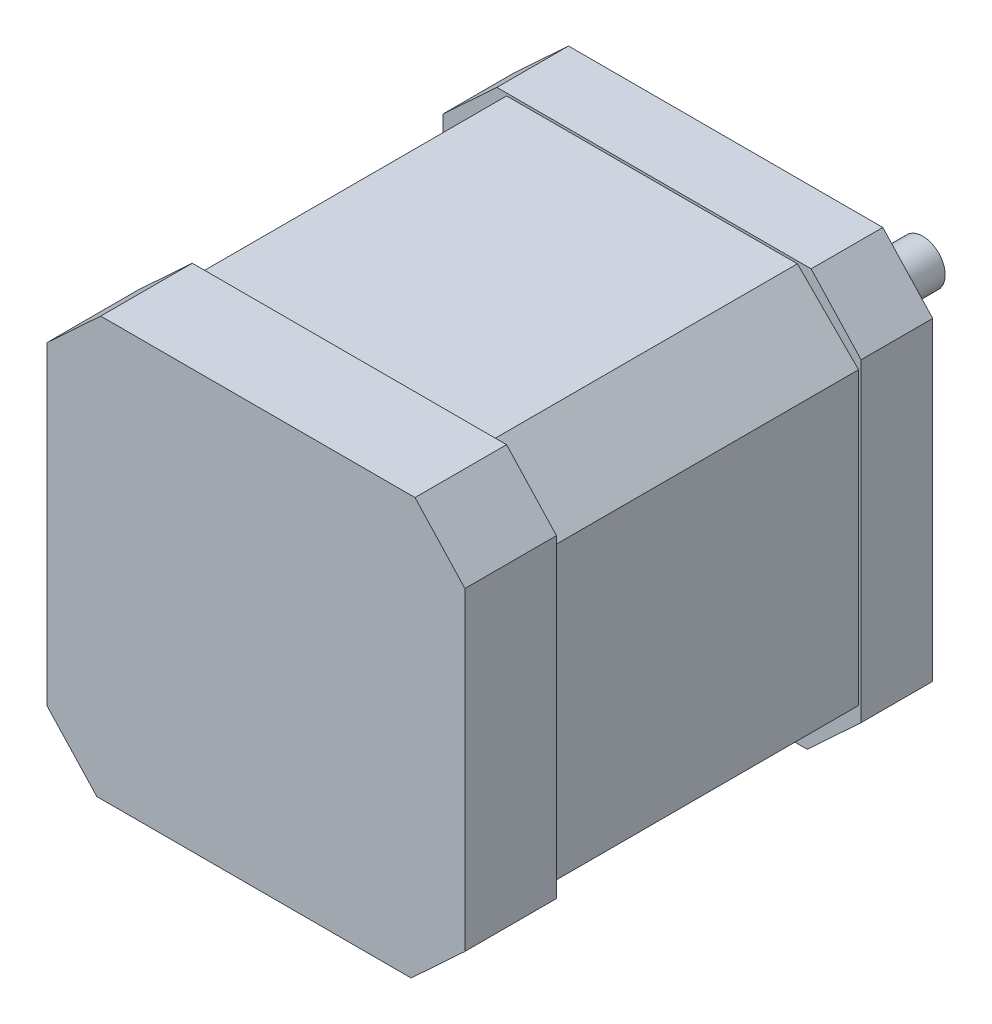
SolidWorks part; units mm, degrees
material "Ferro dúctil"
ref_plane "Plano frontal" through (0, 0, 0) normal (0, 0, 1) x (1, 0, 0)
ref_plane "Plano superior" through (0, 0, 0) normal (0, 1, 0) x (1, 0, 0)
ref_plane "Plano direito" through (0, 0, 0) normal (1, 0, 0) x (0, 0, -1)
sketch "Esboço1" plane through (0, 0, 0) normal (0, 0, 1) x (1, 0, 0)
  line L0 (-1.3818, -36.7436) -> (-36.7436, 1.3818)
  line L1 (-21, 21) -> (21, 21)
  line L2 (-21, 21) -> (-21, -21)
  line L3 (-21, -21) -> (21, -21)
  line L4 (21, 21) -> (21, -21)
  line L5 (-21, 21) -> (21, -21) construction
  line L6 (-21, -21) -> (21, 21) construction
  line L7 (-1.3818, -36.7436) -> (36.7436, -1.3818)
  line L8 (-36.7436, 1.3818) -> (1.3818, 36.7436)
  line L9 (36.7436, -1.3818) -> (1.3818, 36.7436)
  line L10 (-1.3818, -36.7436) -> (1.3818, 36.7436) construction
  line L11 (-36.7436, 1.3818) -> (36.7436, -1.3818) construction
  point P0 (0, 0)
  point P7 (0, 0)
  dimension "D1" = 42
  dimension "D2" = 52
extrude "Ressalto-extrusão1" add sketch "Esboço1" along normal blind 47 contours L4 L9 L1 L8 L2 L0 L3 L7 region at (0, 0, 0)
sketch "Esboço2" plane through (0, 0, 47) normal (0, 0, 1) x (1, 0, 0)
  line L1 (-20.75, -20.75) -> (20.75, -20.75)
  line L2 (-20.75, -20.75) -> (-20.75, 20.75)
  line L3 (-20.75, 20.75) -> (20.75, 20.75)
  line L4 (20.75, -20.75) -> (20.75, 20.75)
  line L5 (-20.75, -20.75) -> (20.75, 20.75) construction
  line L6 (-20.75, 20.75) -> (20.75, -20.75) construction
  line L7 (0, -35.3553) -> (-35.3553, 0)
  line L8 (0, -35.3553) -> (35.3553, 0)
  line L9 (-35.3553, 0) -> (0, 35.3553)
  line L10 (35.3553, 0) -> (0, 35.3553)
  line L11 (0, -35.3553) -> (0, 35.3553) construction
  line L12 (-35.3553, 0) -> (35.3553, 0) construction
  point P0 (0, 0)
  point P8 (-17.6777, 17.6777)
  point P9 (0, 0)
  dimension "D1" = 50
  dimension "D2" = 41.5
extrude "Corte-Extrusão-Fina1" cut sketch "Esboço2" against normal offset from surface (30.6 mm away) 7.2 from offset 9.2 thin contours L4 L10 L3 L9 L2 L7 L1 L8 up to face at (0, 0, 0) offset against normal yes thin type one direction wall 10
sketch "Esboço3" plane through (0, 0, 0) normal (0, 0, -1) x (-1, 0, 0)
  circle A0 centre (0, 0) radius 2.25
  dimension "D1" = 4.5
extrude "Ressalto-extrusão2" add sketch "Esboço3" along normal blind 20
sketch "Esboço4" plane through (0, 0, 0) normal (0, 0, -1) x (-1, 0, 0)
  circle A0 centre (0, 0) radius 10
  dimension "D1" = 20
extrude "Ressalto-extrusão3" add sketch "Esboço4" along normal blind 2
sketch "Esboço5" plane through (0, 0, 0) normal (0, 0, -1) x (-1, 0, 0)
  line L1 (15.5, 15.5) -> (-15.5, 15.5) construction
  line L2 (15.5, 15.5) -> (15.5, -15.5) construction
  line L3 (15.5, -15.5) -> (-15.5, -15.5) construction
  line L4 (-15.5, 15.5) -> (-15.5, -15.5) construction
  line L5 (15.5, 15.5) -> (-15.5, -15.5) construction
  line L6 (15.5, -15.5) -> (-15.5, 15.5) construction
  circle A0 centre (15.5, -15.5) radius 1.5
  circle A1 centre (-15.5, -15.5) radius 1.5
  circle A2 centre (-15.5, 15.5) radius 1.5
  circle A3 centre (15.5, 15.5) radius 1.5
  point P0 (0, 0)
  dimension "D1" = 3
  dimension "D2" = 31
extrude "Corte-extrusão1" cut sketch "Esboço5" against normal blind 10
